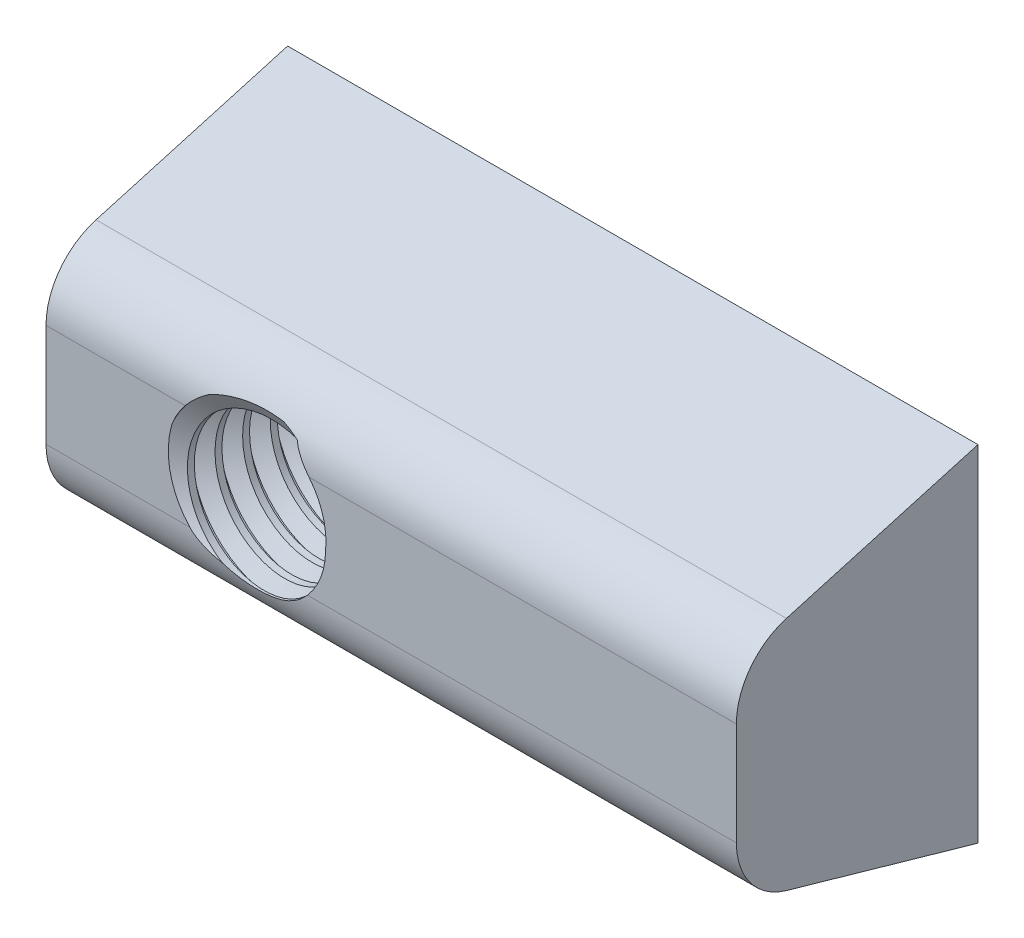
SolidWorks part; units mm, degrees
ref_plane "Front Plane" through (0, 0, 0) normal (0, 0, 1) x (1, 0, 0)
ref_plane "Top Plane" through (0, 0, 0) normal (0, 1, 0) x (1, 0, 0)
ref_plane "Right Plane" through (0, 0, 0) normal (1, 0, 0) x (0, 0, -1)
sketch "Sketch1" plane through (0, 0, 0) normal (0, 0, 1) x (1, 0, 0)
  line L1 (0, 0) -> (20, 0)
  line L2 (0, 0) -> (0, -10)
  line L3 (0, -10) -> (20, -10)
  line L4 (20, 0) -> (20, -10)
  dimension "D1" = 10
  dimension "D2" = 20
extrude "Boss-Extrude1" add sketch "Sketch1" along normal blind 7
sketch "Sketch2" plane through (0, 0, 0) normal (-1, 0, 0) x (0, 0, 1)
  line L0 (0, 0) -> (7, -2)
  line L1 (7, 0) -> (7, -10) construction
  line L2 (0, -10) -> (7, -8)
  line L4 (7, 0) -> (0, 0) construction
  line L5 (7, -10) -> (0, -10) construction
  line L6 (7, -2) -> (7, 0)
  line L7 (7, 0) -> (0, 0)
  line L8 (7, -8) -> (7, -10)
  line L9 (7, -10) -> (0, -10)
  dimension "D1" = 2
  dimension "D2" = 2
extrude "Cut-Extrude1" cut sketch "Sketch2" against normal through all
fillet "Fillet1" radius 2 2 edges at (10, -2, 7) (10, -8, 7)
hole_wizard "Ø4.2 (4.2) Diameter Hole1" positions "Sketch3" profile "Sketch4" hole size "Ø4.2" standard "ISO"
sketch "Sketch3" plane through (0, 0, 7) normal (0, 0, 1) x (1, 0, 0)
  line L0 (0, -3.5086) -> (0, -6.4914) construction
  point P0 (6, -5.0996)
  dimension "D1" = 6
sketch "Sketch4" plane through (6, -5.0996, 7) normal (1, 0, 0) x (0, -1, 0)
  line L0 (0, 0) -> (0, 9.2618)
  line L1 (0, 9.2618) -> (2.1, 8)
  line L2 (2.1, 8) -> (2.1, 0)
  line L5 (2.1, 0) -> (0, 0)
  line L10 (0, 9.2618) -> (-2.1, 8) construction
  line L11 (0, -6.35) -> (0, 107.95) construction
  dimension "Hole Dia." = 4.2
  dimension "Hole Depth" = 8
  dimension "Drill Angle" = 118
thread "Thread1" pitch 0.8 method cut profile "Thread Profile1" start angle 0, offset 0, length 7, pitch 0.8, diameter 4.2
ref_plane "Plane1" through (8.1, -5.0996, 0) normal (0, -1, 0) x (1, 0, 0)
sketch "Thread Profile1" plane through (8.1, -5.0996, 0) normal (0, -1, 0) x (1, 0, 0)
  line L0 (0, 0) -> (0, 0.8) construction
  line L1 (0, 0) -> (0.433, 0.25)
  line L2 (0.433, 0.25) -> (0.433, 0.35)
  line L3 (0.433, 0.35) -> (0, 0.6)
  line L4 (0.433, 0.3) -> (0, 0.3) construction
  line L11 (0, 0) -> (0, 0.6)
  point P2 (0, 0)
  dimension "Pitch" = 0.8
  dimension "Profile_Angle" = 60
  dimension "Profile_Land" = 0.1
  dimension "Profile_Height" = 0.433
